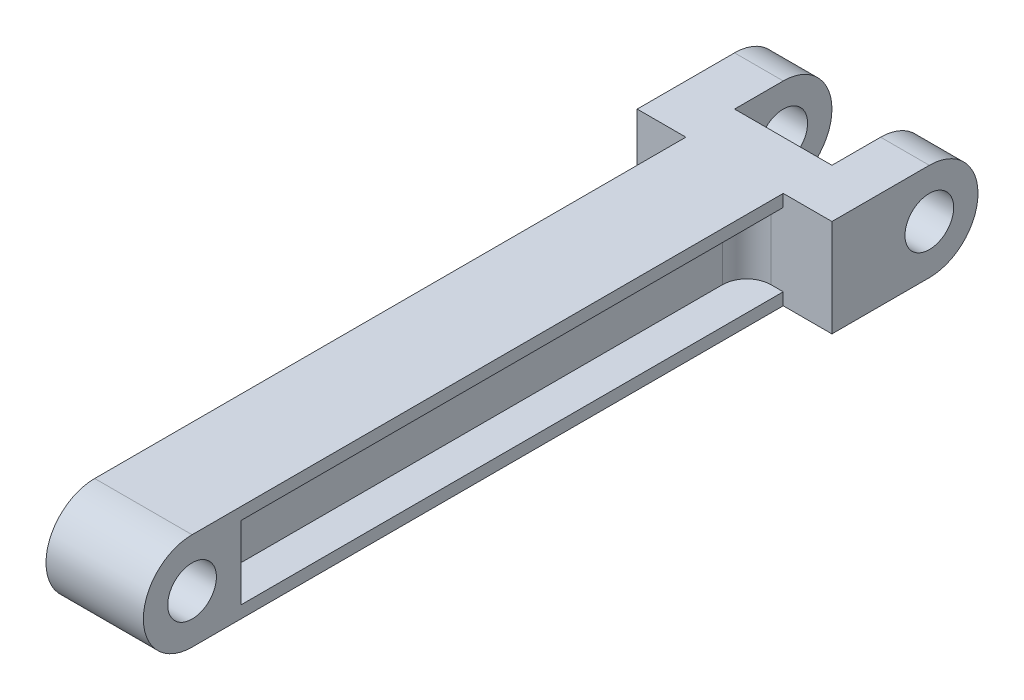
SolidWorks part; units mm, degrees
material "Plain Carbon Steel"
ref_plane "Front" through (0, 0, 0) normal (0, 0, 1) x (1, 0, 0)
ref_plane "Top" through (0, 0, 0) normal (0, 1, 0) x (1, 0, 0)
ref_plane "Right" through (0, 0, 0) normal (1, 0, 0) x (0, 0, -1)
sketch "Sketch3" plane through (0, 0, 0) normal (0, 1, 0) x (1, 0, 0)
  line L1 (0, 0) -> (1.5875, 0)
  line L2 (0, 0) -> (0, 89.8026)
  line L3 (0, 89.8026) -> (1.5875, 89.8026)
  line L4 (1.5875, 0) -> (1.5875, 89.8026)
  dimension "D1" = 89.8026
  dimension "D2" = 1.5875
extrude "Boss-Extrude2" add sketch "Sketch3" along normal blind 12.7
sketch "Sketch4" plane through (1.5875, 0, 0) normal (1, 0, 0) x (0, 0, -1)
  line L0 (0, 12.7) -> (0, 0) construction
  line L1 (89.8026, 12.7) -> (89.8026, 0) construction
  line L2 (6.35, 12.7) -> (6.35, 0)
  line L3 (0, 0) -> (89.8026, 0) construction
  line L4 (83.4526, 12.7) -> (83.4526, 0)
  line L5 (0, 12.7) -> (89.8026, 12.7) construction
  line L6 (6.35, 12.7) -> (0, 12.7)
  line L7 (6.35, 12.7) -> (6.35, 0)
  line L8 (6.35, 0) -> (0, 0)
  line L9 (0, 12.7) -> (0, 0)
  line L10 (89.8026, 12.7) -> (83.4526, 12.7)
  line L11 (89.8026, 12.7) -> (89.8026, 0)
  line L12 (89.8026, 0) -> (83.4526, 0)
  line L13 (83.4526, 12.7) -> (83.4526, 0)
  line L14 (83.4526, 0) -> (77.1026, 0)
  line L15 (83.4526, 0) -> (83.4526, 12.7)
  line L16 (83.4526, 12.7) -> (77.1026, 12.7)
  line L17 (77.1026, 0) -> (77.1026, 12.7)
  circle A0 centre (0, 6.35) radius 6.35
  circle A1 centre (0, 6.35) radius 3.175
  circle A2 centre (89.8026, 6.35) radius 6.35
  circle A3 centre (89.8026, 6.35) radius 3.175
  point P17 (6.35, 6.35)
  point P20 (83.4526, 6.35)
  line M4 (0, 0) -> (89.8026, 0)
  line M5 (89.8026, 0) -> (89.8026, 12.7)
  line M6 (89.8026, 12.7) -> (0, 12.7)
  line M7 (0, 12.7) -> (0, 0)
  dimension "D1" = 6.35
  dimension "D2" = 6.35
  dimension "D3" = 6.35
extrude "Boss-Extrude4" add sketch "Sketch4" against normal blind 6.35 contours A1 A0 M7 | A1 A0 M7 | A0 L7 M4 | A0 L2 M6 region at (1.5875, 11.2816, -4.9316) region at (1.5875, 1.9603, -4.3897) region at (1.5875, 1.4184, -4.9316) region at (1.5875, 11.1125, 0.142)
extrude "Boss-Extrude5" add sketch "Sketch4<6>" against normal blind 12.7 contours L17 L15 L4 M4 M6 region at (1.5875, 6.35, -80.2776)
sketch "Sketch4<6>" plane through (1.5875, 0, 0) normal (1, 0, 0) x (0, 0, -1) same geometry as "Sketch4"
extrude "Boss-Extrude6" add sketch "Sketch4<7>" against normal up to surface (12.7 mm away) from offset 6.35 contours A3 A2 M5 | A3 A2 M5 | A2 L15 M4 | A2 L4 M6 region at (1.5875, 11.2816, -84.8709) region at (1.5875, 1.4184, -84.8709) region at (1.5875, 10.7397, -85.4128) region at (1.5875, 10.7397, -94.1923) up to face at (-11.1125, 6.35, -80.2776) offset against normal yes
sketch "Sketch4<7>" plane through (1.5875, 0, 0) normal (1, 0, 0) x (0, 0, -1) same geometry as "Sketch4"
extrude "Cut-Extrude1" cut sketch "Sketch4<9>" against normal up to surface (1.5875 mm away) contours A2 L15 M4 | A3 A2 M5 | A2 L4 M6 | A3 region at (1.5875, 11.2816, -84.8709) region at (1.5875, 1.4184, -84.8709) region at (1.5875, 10.7397, -85.4128) up to face at (0, 6.35, -86.6276)
sketch "Sketch4<9>" plane through (1.5875, 0, 0) normal (1, 0, 0) x (0, 0, -1) same geometry as "Sketch4"
sketch "Sketch5" plane through (0, 0, -6.35) normal (0, 0, -1) x (-1, 0, 0)
  line L0 (0, 12.7) -> (0, 0) construction
  line L1 (4.7625, 12.7) -> (0, 12.7)
  line L2 (4.7625, 12.7) -> (4.7625, 11.1125)
  line L3 (4.7625, 11.1125) -> (0, 11.1125)
  line L4 (0, 12.7) -> (0, 11.1125)
  line L5 (4.7625, 12.7) -> (4.7625, 0) construction
  line L6 (0, 0) -> (4.7625, 0)
  line L7 (0, 0) -> (0, 1.5875)
  line L8 (0, 1.5875) -> (4.7625, 1.5875)
  line L9 (4.7625, 0) -> (4.7625, 1.5875)
  dimension "D1" = 1.5875
  dimension "D2" = 1.5875
extrude "Boss-Extrude7" add sketch "Sketch5" along normal up to surface (70.7526 mm away) up to face at (-5.5562, 6.35, -77.1026)
extrude "Cut-Extrude2" cut sketch "Sketch4<10>" against normal blind 12.7 contours L9 A1 region at (1.5875, 6.35, -1.3475)
sketch "Sketch4<10>" plane through (1.5875, 0, 0) normal (1, 0, 0) x (0, 0, -1) same geometry as "Sketch4"
fillet "Fillet1" radius 3.175 1 edges at (0, 6.35, -77.1026)
fillet "Fillet2" radius 3.175 1 edges at (0, 6.35, -6.35)
ref_plane "Plane1" through (1.5875, 0, 0) normal (1, 0, 0) x (0, 0, -1)
mirror "Mirror3" about plane through (1.5875, 0, 0) normal (1, 0, 0) of "Fillet2", "Fillet1", "Cut-Extrude2", "Boss-Extrude7", "Cut-Extrude1", "Boss-Extrude6", "Boss-Extrude5", "Boss-Extrude4", "Boss-Extrude2"
